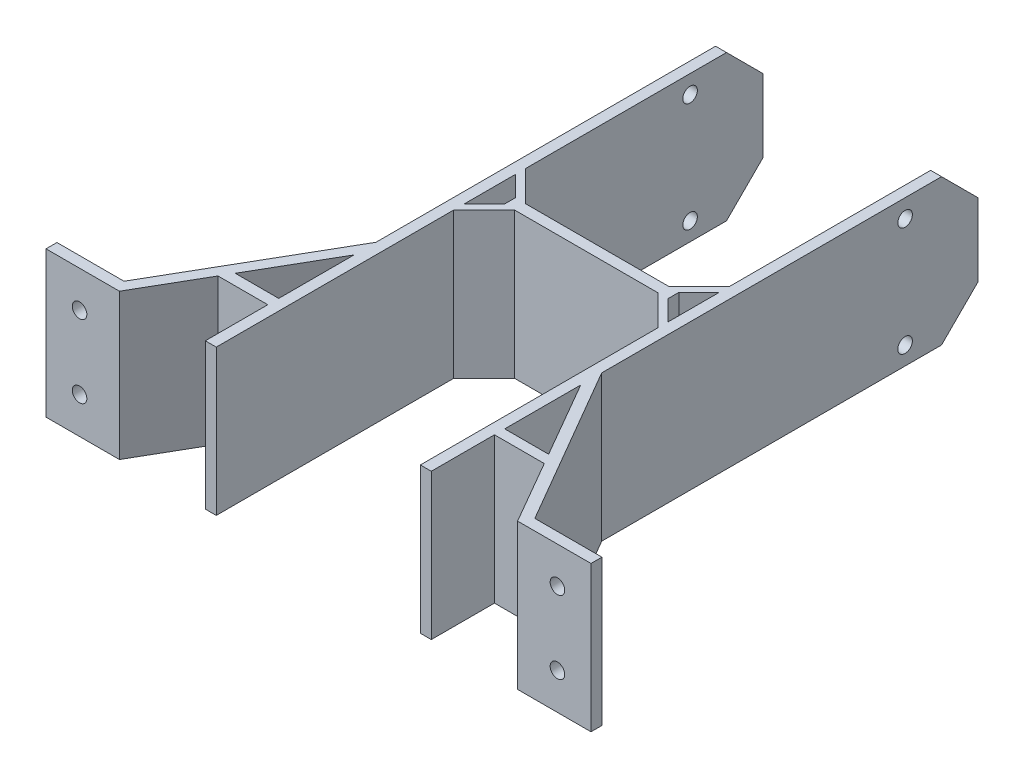
SolidWorks part; units mm, degrees
ref_plane "Alzado" through (0, 0, 0) normal (0, 0, 1) x (1, 0, 0)
ref_plane "Planta" through (0, 0, 0) normal (0, 1, 0) x (1, 0, 0)
ref_plane "Vista lateral" through (0, 0, 0) normal (1, 0, 0) x (0, 0, -1)
sketch "Croquis1" plane through (0, 0, 0) normal (0, 1, 0) x (1, 0, 0)
  line L0 (-32.5, 0) -> (32.5, 0) construction
  line L1 (-28, 9.8655) -> (-19.6345, 1.5)
  line L2 (-28, -75) -> (-31, -75)
  line L3 (-28, -75) -> (-28, -9.8655)
  line L4 (-28, 75) -> (-31, 75)
  line L5 (-31, -75) -> (-31, -57.8568)
  line L6 (-28, -75) -> (-31, 75) construction
  line L7 (-28, 75) -> (-31, -75) construction
  line L8 (31, -75) -> (28, -75)
  line L9 (31, -75) -> (31, -57.6674)
  line L10 (31, 75) -> (28, 75)
  line L11 (28, -75) -> (28, -9.8655)
  line L12 (31, -75) -> (28, 75) construction
  line L13 (31, 75) -> (28, -75) construction
  line L14 (-19.6345, 1.5) -> (19.6345, 1.5)
  line L15 (19.6345, 1.5) -> (28, 9.8655)
  line L16 (-28, -9.8655) -> (-19.6345, -1.5)
  line L17 (-19.6345, -1.5) -> (19.6345, -1.5)
  line L18 (19.6345, -1.5) -> (28, -9.8655)
  line L19 (0, 1.5) -> (0, -1.5) construction
  line L20 (-28, -7.037) -> (-22.455, -1.492)
  line L21 (-22.455, -1.492) -> (-22.455, 1.492)
  line L22 (-22.455, 1.492) -> (-28, 7.037)
  line L23 (28, -7.0117) -> (22.455, -1.4667)
  line L24 (22.455, -1.4667) -> (22.455, 1.4667)
  line L25 (22.455, 1.4667) -> (28, 7.0117)
  line L26 (-28, 9.8655) -> (-28, 75)
  line L27 (-28, -7.037) -> (-28, 7.037)
  line L28 (28, -7.0117) -> (28, 7.0117)
  line L29 (28, 9.8655) -> (28, 75)
  line L30 (31, -33.9913) -> (43.0467, -54.8568)
  line L31 (54.6764, -75) -> (74.8206, -75)
  line L32 (74.8206, -75) -> (74.8206, -72)
  line L33 (74.8206, -72) -> (56.4084, -72)
  line L34 (56.4084, -72) -> (31, -28.244)
  line L35 (-31, -34.1807) -> (-42.9373, -54.8568)
  line L36 (-54.567, -75) -> (-74.7113, -75)
  line L37 (-74.7113, -75) -> (-74.7113, -72)
  line L38 (-74.7113, -72) -> (-56.2991, -72)
  line L39 (-56.2991, -72) -> (-31, -28.1807)
  line L40 (-44.6694, -57.8568) -> (-31, -57.8568)
  line L41 (-42.9373, -54.8568) -> (-31, -54.8568)
  line L42 (44.6694, -57.6674) -> (31, -57.6674)
  line L43 (43.0467, -54.8568) -> (31, -54.8568)
  line L44 (-44.6694, -57.8568) -> (-54.567, -75)
  line L45 (-31, -54.8568) -> (-31, -34.1807)
  line L46 (-31, -28.1807) -> (-31, 75)
  line L47 (44.6694, -57.6674) -> (54.6764, -75)
  line L48 (31, -54.8568) -> (31, -33.9913)
  line L49 (31, -28.244) -> (31, 75)
  point P3 (29.5, 0)
  point P4 (0, 0)
  point P7 (-29.5, 0)
  point P20 (0, 0)
  point P23 (0, 1.5)
  point P24 (0, -1.5)
  point P34 (22.455, 0)
  dimension "D1" = 3
  dimension "D2" = 56
  dimension "D3" = 3
  dimension "D4" = 2
  dimension "D5" = 2
  dimension "D6" = 150
  dimension "D7" = 60
  dimension "D8" = 60
  dimension "D9" = 3
  dimension "D10" = 3
  dimension "D11" = 3
extrude "Saliente-Extruir1" add sketch "Croquis1" along normal blind 40
sketch "Croquis2" plane through (31, 0, 0) normal (1, 0, 0) x (0, 0, -1)
  line L0 (75, 40) -> (75, 0) construction
  line L1 (55, 35) -> (55, 5) construction
  line L2 (-75, 40) -> (-57.6674, 40) construction
  circle A0 centre (55, 35) radius 2
  circle A1 centre (55, 5) radius 2
  point P4 (55, 20)
  dimension "D1" = 4
  dimension "D2" = 20
  dimension "D3" = 20
  dimension "D4" = 30
extrude "Cortar-Extruir1" cut sketch "Croquis2" against normal through all
chamfer "Chaflán1" distance 10 angle 45 4 edges at (-29.5, 40, -75) (-29.5, 0, -75) (29.5, 0, -75) (29.5, 40, -75)
sketch "Croquis3" plane through (0, 0, 72) normal (0, 0, -1) x (-1, 0, 0)
  line L1 (-74.8206, 40) -> (-56.4084, 40) construction
  line L2 (-74.8206, 0) -> (-56.4084, 0) construction
  circle A0 centre (-65.6145, 30) radius 2
  circle A1 centre (-65.6145, 10) radius 2
  circle A2 centre (65.5052, 30) radius 2
  circle A3 centre (65.5052, 10) radius 2
  point P12 (0, 0)
  point P13 (0, 0)
  point P14 (0, 0)
  dimension "D1" = 4
  dimension "D2" = 10
  dimension "D3" = 10
extrude "Cortar-Extruir2" cut sketch "Croquis3" against normal through all
